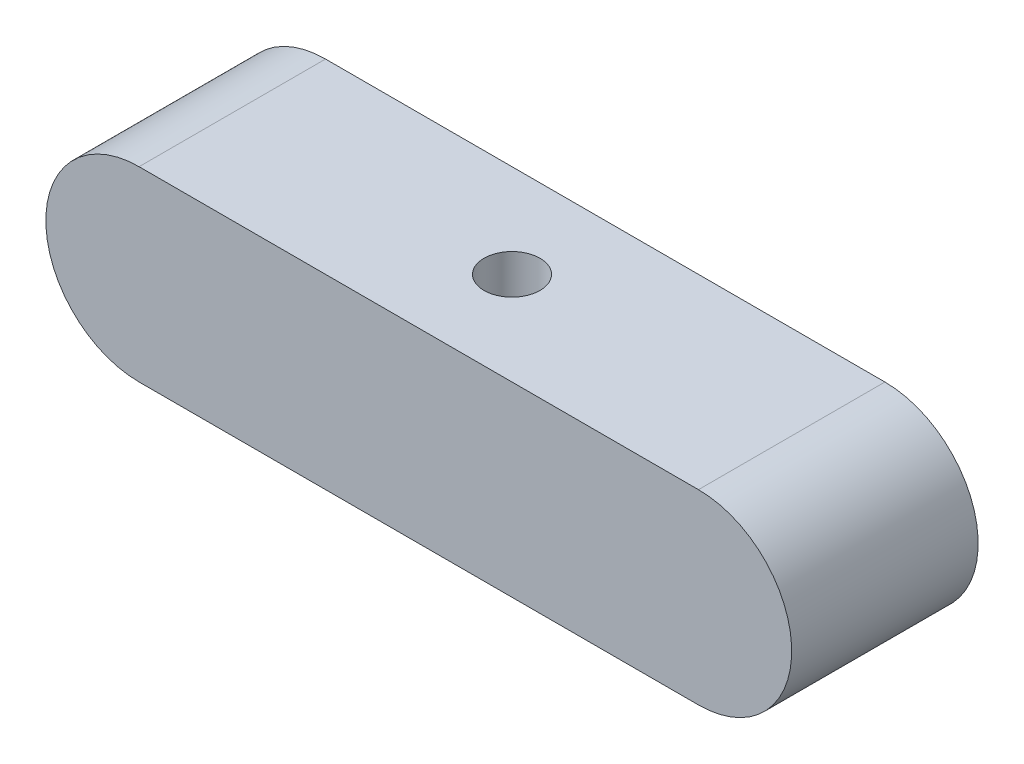
SolidWorks part; units mm, degrees
ref_plane "Front Plane" through (0, 0, 0) normal (0, 0, 1) x (1, 0, 0)
ref_plane "Top Plane" through (0, 0, 0) normal (0, 1, 0) x (1, 0, 0)
ref_plane "Right Plane" through (0, 0, 0) normal (1, 0, 0) x (0, 0, -1)
sketch "Sketch1" plane through (0, 0, 0) normal (0, 0, 1) x (1, 0, 0)
  line L0 (0, 0) -> (30, 0) construction
  line L1 (0, 5) -> (30, 5)
  line L2 (0, -5) -> (30, -5)
  arc A0 (0, 5) -> (0, -5) centre (0, 0) ccw
  arc A1 (30, -5) -> (30, 5) centre (30, 0) ccw
  point P3 (15, 0)
  dimension "D1" = 5
  dimension "D2" = 30
extrude "Boss-Extrude1" add sketch "Sketch1" along normal blind 10
sketch "Sketch2" plane through (0, 5, 0) normal (0, 1, 0) x (1, 0, 0)
  line L0 (30, -10) -> (0, -10) construction
  line L1 (30, -10) -> (30, 0) construction
  circle A0 centre (15, -5) radius 1.5
  point P2 (0, 0)
  point P5 (15, -10)
  point P8 (30, -5)
  dimension "D1" = 3
extrude "Cut-Extrude1" cut sketch "Sketch2" against normal through all
